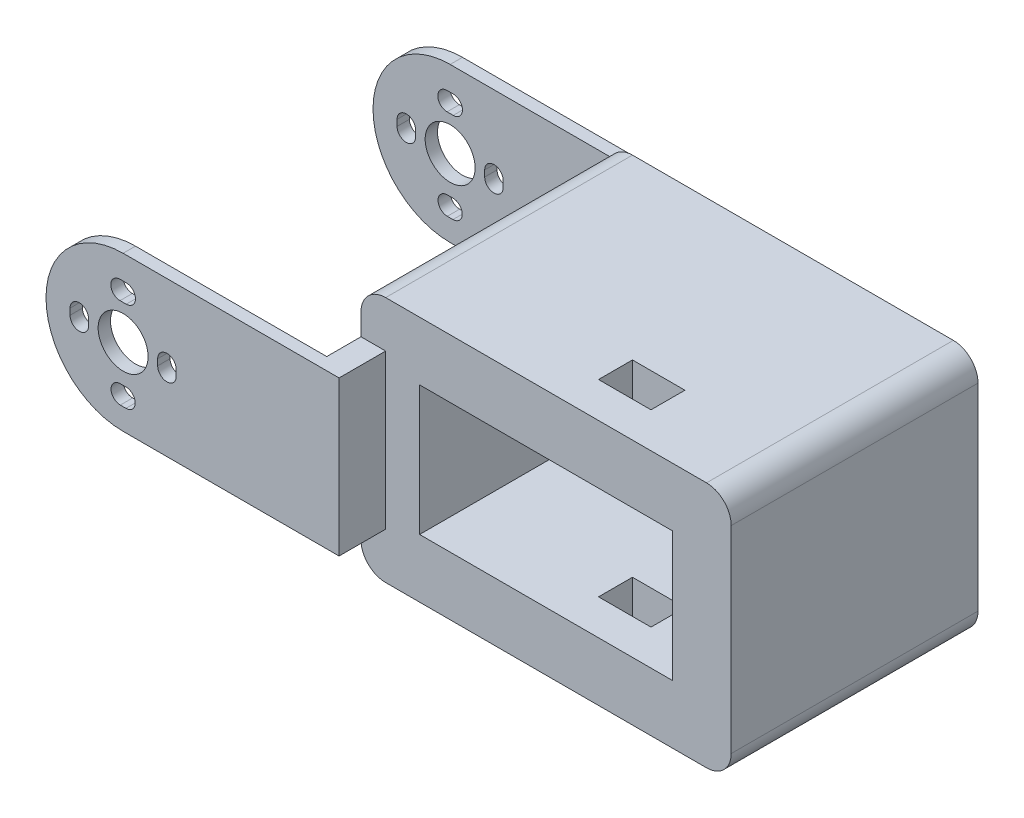
SolidWorks part; units mm, degrees
ref_plane "前基準面" through (0, 0, 0) normal (0, 0, 1) x (1, 0, 0)
ref_plane "上基準面" through (0, 0, 0) normal (0, 1, 0) x (1, 0, 0)
ref_plane "右基準面" through (0, 0, 0) normal (1, 0, 0) x (0, 0, -1)
sketch "Sketch1" plane through (0, 0, 0) normal (0, 0, 1) x (1, 0, 0)
  line L0 (-29.0958, -5.1361) -> (30.9042, -5.1361) construction
  line L1 (-19.5958, 5.3639) -> (21.4042, 5.3639)
  line L2 (-19.5958, 5.3639) -> (-19.5958, -15.6361)
  line L3 (-19.5958, -15.6361) -> (21.4042, -15.6361)
  line L4 (21.4042, 5.3639) -> (21.4042, -15.6361)
  line L5 (-29.0958, 14.8639) -> (30.9042, 14.8639)
  line L6 (-29.0958, 14.8639) -> (-29.0958, -25.1361)
  line L7 (-29.0958, -25.1361) -> (30.9042, -25.1361)
  line L8 (30.9042, 14.8639) -> (30.9042, -25.1361)
  line L9 (0.9042, 14.8639) -> (0.9042, -25.1361) construction
  line L10 (21.4042, -5.1361) -> (-19.5958, -5.1361) construction
  line L11 (0.9042, 5.3639) -> (0.9042, -15.6361) construction
  point P16 (0.9042, -5.1361)
  point P17 (0.9042, -5.1361)
  dimension "D1" = 21
  dimension "D2" = 41
  dimension "D3" = 60
  dimension "D4" = 40
extrude "Boss-Extrude1" add sketch "Sketch1" along normal blind 40
sketch "Sketch2" plane through (0, 0, 40) normal (0, 0, 1) x (1, 0, 0)
  line L0 (-19.5958, -5.1361) -> (-29.0958, -5.1361) construction
  line L1 (-25.0958, -5.1361) -> (-29.0958, -5.1361) construction
  line L3 (-29.0958, 14.8639) -> (-29.0958, -25.1361) construction
  line L4 (-19.5958, 5.3639) -> (-19.5958, -15.6361) construction
  line L5 (-29.0958, 7.3639) -> (-25.0958, 7.3639)
  line L6 (-29.0958, 7.3639) -> (-29.0958, -17.6361)
  line L7 (-29.0958, -17.6361) -> (-25.0958, -17.6361)
  line L8 (-25.0958, 7.3639) -> (-25.0958, -17.6361)
  dimension "D1" = 25
  dimension "D2" = 4
extrude "Boss-Extrude2" add sketch "Sketch2" along normal blind 5.55
extrude "Boss-Extrude3" add sketch "Sketch2<2>" against normal blind 45.55
sketch "Sketch2<2>" plane through (0, 0, 40) normal (0, 0, 1) x (1, 0, 0) same geometry as "Sketch2"
sketch "Sketch3" plane through (0, 0, 45.55) normal (0, 0, 1) x (1, 0, 0)
  line L0 (-60.5958, 1.9639) -> (-59.5958, 1.9639) construction
  line L1 (-25.0958, 7.3639) -> (-60.0958, 7.3639)
  line L2 (-25.0958, 7.3639) -> (-25.0958, -17.6361)
  line L3 (-25.0958, -17.6361) -> (-60.0958, -17.6361)
  line L4 (-60.0958, 7.3639) -> (-60.0958, -17.6361)
  line L5 (-60.5958, 3.4639) -> (-59.5958, 3.4639)
  line L6 (-60.5958, 0.4639) -> (-59.5958, 0.4639)
  line L7 (-60.0958, 7.3639) -> (-60.0958, -17.6361) construction
  line L8 (-60.5559, -12.6762) -> (-59.6357, -12.6762) construction
  line L9 (-60.5559, -11.1762) -> (-59.6357, -11.1762)
  line L10 (-60.5559, -14.1762) -> (-59.6357, -14.1762)
  line L11 (-60.0958, -5.1361) -> (-72.5958, -5.1361) construction
  line L12 (-67.1958, -4.6361) -> (-67.1958, -5.6361) construction
  line L15 (-65.6958, -4.6361) -> (-65.6958, -5.6361)
  line L16 (-68.6958, -4.6361) -> (-68.6958, -5.6361)
  line L17 (-52.9958, -4.6361) -> (-52.9958, -5.6361) construction
  line L18 (-51.4958, -4.6361) -> (-51.4958, -5.6361)
  line L19 (-54.4958, -4.6361) -> (-54.4958, -5.6361)
  line L20 (-60.0958, -5.1361) -> (-25.0958, -5.1361) construction
  arc A0 (-60.0958, 7.3639) -> (-60.0958, -17.6361) centre (-60.0958, -5.1361) ccw
  circle A1 centre (-60.0958, -5.1361) radius 4.05
  arc A3 (-60.5958, 3.4639) -> (-60.5958, 0.4639) centre (-60.5958, 1.9639) ccw
  arc A4 (-59.5958, 0.4639) -> (-59.5958, 3.4639) centre (-59.5958, 1.9639) ccw
  arc A5 (-60.5559, -11.1762) -> (-60.5559, -14.1762) centre (-60.5559, -12.6762) ccw
  arc A6 (-59.6357, -14.1762) -> (-59.6357, -11.1762) centre (-59.6357, -12.6762) ccw
  arc A9 (-65.6958, -4.6361) -> (-68.6958, -4.6361) centre (-67.1958, -4.6361) ccw
  arc A10 (-68.6958, -5.6361) -> (-65.6958, -5.6361) centre (-67.1958, -5.6361) ccw
  arc A11 (-51.4958, -4.6361) -> (-54.4958, -4.6361) centre (-52.9958, -4.6361) ccw
  arc A12 (-54.4958, -5.6361) -> (-51.4958, -5.6361) centre (-52.9958, -5.6361) ccw
  point P9 (-60.0958, 1.9639)
  point P14 (-58.0958, 1.9639)
  point P15 (-62.0958, 1.9639)
  point P19 (-60.0958, -12.6762)
  point P25 (-67.1958, -5.1361)
  point P31 (-67.1958, -3.1361)
  point P32 (-67.1958, -7.1361)
  point P34 (-65.6958, -5.1361)
  point P37 (-52.9958, -5.1361)
  point P42 (-52.9958, -3.1361)
  point P43 (-52.9958, -7.1361)
  line M15 (-29.0958, 7.3639) -> (-29.0958, -17.6361)
  line M16 (-29.0958, -17.6361) -> (-25.0958, -17.6361)
  line M17 (-25.0958, -17.6361) -> (-25.0958, 7.3639)
  line M18 (-25.0958, 7.3639) -> (-29.0958, 7.3639)
  dimension "D2" = 4
  dimension "D10" = 5.6
  dimension "D9" = 4
  dimension "D1" = 35
  dimension "D3" = 3
  dimension "D4" = 5.6
  dimension "D5" = 25
  dimension "D6" = 6.0402
  dimension "D7" = 0
  dimension "D8" = 3
  dimension "D11" = 5.6
  dimension "D12" = 3
  dimension "D13" = 4
extrude "Boss-Extrude6" add sketch "Sketch3" along normal blind 2 contours A5 L9 L4 A1 L6 A3 L5 A0 L10 A10 L16 A9 L15 | A6 L10 L4 L3 L1 L5 A4 L6 A1 L9 A12 L19 A11 L18 M15 | M18 M15 M16 M17 region at (-27.0958, -5.1361, 45.55) region at (-43.7932, -5.1343, 45.55) region at (-60.3753, 5.4139, 45.55)
extrude "Boss-Extrude7" add sketch "Sketch3<8>" against normal blind 53 contours A5 L9 L4 A1 L6 A3 L5 A0 L10 A10 L16 A9 L15 | A6 L10 L4 L3 L1 L5 A4 L6 A1 L9 A12 L19 A11 L18 M15 | M18 M15 M16 M17 region at (-27.0958, -5.1361, 45.55) region at (-43.7932, -5.1343, 45.55) region at (-60.3753, 5.4139, 45.55)
sketch "Sketch3<8>" plane through (0, 0, 45.55) normal (0, 0, 1) x (1, 0, 0) same geometry as "Sketch3"
extrude "Cut-Extrude1" cut sketch "Sketch3<11>" against normal blind 51 contours A6 L10 L4 L3 L1 L5 A4 L6 A1 L9 A12 L19 A11 L18 M15 | A5 L9 L4 A1 L6 A3 L5 A0 L10 A10 L16 A9 L15 region at (-43.7932, -5.1343, 45.55) region at (-60.3753, 5.4139, 45.55)
sketch "Sketch3<11>" plane through (0, 0, 45.55) normal (0, 0, 1) x (1, 0, 0) same geometry as "Sketch3"
sketch "草圖1" plane through (0, 14.8639, 0) normal (0, 1, 0) x (1, 0, 0)
  line L0 (30.9042, -40) -> (30.9042, 0) construction
  line L1 (12.1542, -34.25) -> (3.6542, -34.25)
  line L2 (12.1542, -34.25) -> (12.1542, -28.75)
  line L3 (12.1542, -28.75) -> (3.6542, -28.75)
  line L4 (3.6542, -34.25) -> (3.6542, -28.75)
  line L5 (30.9042, -40) -> (-29.0958, -40) construction
  dimension "D1" = 8.5
  dimension "D2" = 5.5
  dimension "D3" = 18.75
  dimension "D4" = 5.75
extrude "除料-伸長1" cut sketch "草圖1" against normal blind 40
fillet "圓角2" radius 4 1 edges at (-29.0958, -25.1361, 20) type face fillet first side face at (7.9042, -25.1361, 31.5) second side face at (-29.0958, -5.1361, 20.0167)
fillet "圓角3" radius 4 1 edges at (30.9042, -25.1361, 20) type face fillet first side face at (7.9042, -25.1361, 31.5) second side face at (30.9042, -5.1361, 20)
fillet "圓角4" radius 4 1 edges at (30.9042, 14.8639, 20) type face fillet first side face at (30.9042, -3.1361, 20) second side face at (7.9042, 14.8639, 31.5)
fillet "圓角5" radius 4 1 edges at (-29.0958, 14.8639, 20) type face fillet first side face at (7.9042, 14.8639, 31.5) second side face at (-29.0958, -4.4694, 20.0167)
sketch "Sketch4" plane through (-29.0958, 0, 0) normal (-1, 0, 0) x (0, 0, 1)
  line L0 (-7.45, -5.1361) -> (47.55, -5.1361) construction
  line L1 (20, 14.8639) -> (20, -25.1361) construction
  line L2 (-7.45, 7.3639) -> (-7.45, -17.6361) construction
  line L3 (47.55, -17.6361) -> (47.55, 7.3639) construction
  line L5 (0, 14.8639) -> (40, 14.8639) construction
  line L6 (40, -25.1361) -> (0, -25.1361) construction
  ellipse E0 centre (20.05, -5.1361) end of major axis (59.4905, -5.0518) minor radius 23.4083
  point P12 (20.05, -5.1361)
  point P13 (59.4906, -5.1361)
  point P14 (20, 18.2722)
  point P15 (0, 0)
  dimension "D1" = 78.8811
  dimension "D2" = 46.8166
